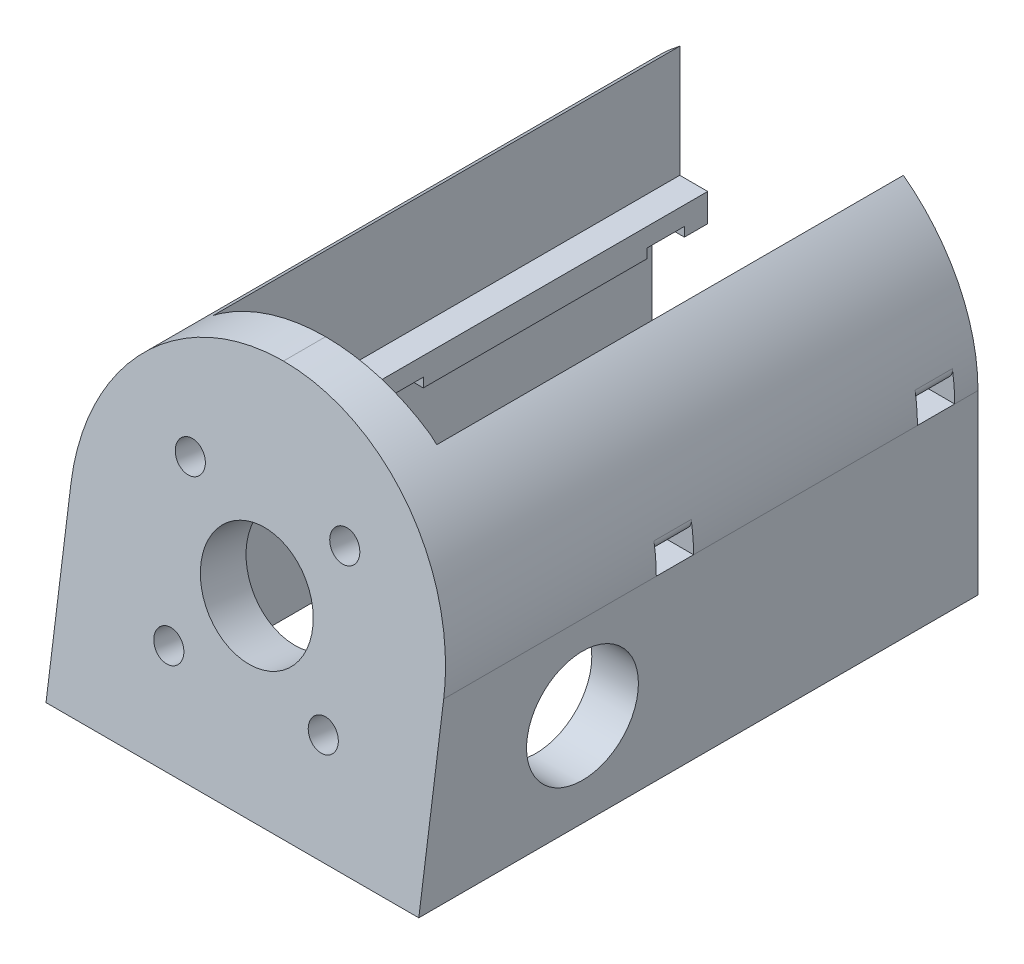
SolidWorks part; units mm, degrees
material "Shapeways \"strong flex\""
ref_plane "Front Plane" through (0, 0, 0) normal (0, 0, 1) x (1, 0, 0)
ref_plane "Top Plane" through (0, 0, 0) normal (0, 1, 0) x (1, 0, 0)
ref_plane "Right Plane" through (0, 0, 0) normal (1, 0, 0) x (0, 0, -1)
sketch "Sketch1" plane through (0, 0, 0) normal (1, 0, 0) x (0, 0, -1)
  line L0 (0, 0) -> (6.961, 49.53)
  line L1 (6.961, 49.53) -> (76.2, 49.53)
  line L2 (76.2, 0) -> (76.2, 49.53)
  line L3 (76.2, 0) -> (0, 0)
  dimension "D3" = 49.53
  dimension "D1" = 82
  dimension "D2" = 76.2
extrude "Boss-Extrude1" add sketch "Sketch1" along normal blind 25.4 and the other way blind 25.4 contours L3 L1 L0 region at (0, 24.3699, -39.8125)
sketch "Sketch3" plane through (0, 0, 0) normal (0, -1, 0) x (1, 0, 0)
  line L1 (0, -6.961) -> (0, -76.2) construction
  line L3 (-25.4, 0) -> (25.4, 0) construction
  circle A2 centre (0, -25.4) radius 8.382
  circle A4 centre (0, -63.246) radius 8.382
  dimension "D3" = 16.764
  dimension "D5" = 16.764
  dimension "D7" = 25.4
  dimension "D8" = 63.246
extrude "Cut-Extrude9" cut sketch "Sketch3" against normal through all contours A4 | A2 region at (0, 0, -63.246)
sketch "Sketch9" plane through (0, 0, -76.2) normal (0, 0, -1) x (-1, 0, 0)
  line L0 (-15.24, 49.53) -> (-15.24, 29.21)
  line L1 (-15.24, 29.21) -> (-11.43, 29.21)
  line L2 (15.24, 29.21) -> (15.24, 49.53)
  line L3 (15.24, 49.53) -> (-15.24, 49.53)
  line L5 (-11.43, 29.21) -> (-11.43, 25.4)
  line L6 (-25.4, 0) -> (-25.4, 49.53) construction
  line L7 (11.43, 25.4) -> (11.43, 29.21)
  line L8 (11.43, 29.21) -> (15.24, 29.21)
  line L9 (-11.43, 25.4) -> (-19.05, 25.4)
  line L10 (-19.05, 25.4) -> (-19.05, 0)
  line L11 (-19.05, 0) -> (19.05, 0)
  line L12 (19.05, 0) -> (19.05, 25.4)
  line L13 (19.05, 25.4) -> (11.43, 25.4)
  line L14 (25.4, 0) -> (25.4, 49.53) construction
  line L17 (25.4, 49.53) -> (-25.4, 49.53) construction
  dimension "D10" = 3.81
  dimension "D11" = 3.81
  dimension "D1" = 20.32
  dimension "D2" = 30.48
  dimension "D3" = 3.81
  dimension "D4" = 10.16
  dimension "D5" = 3.81
  dimension "D6" = 49.53
  dimension "D7" = 6.35
  dimension "D8" = 6.35
  dimension "D9" = 0
extrude "Cut-Extrude14" cut sketch "Sketch9" against normal blind 63.5 contours L3 L0 L1 L5 L9 L10 L11 L12 L13 L7 L8 L2
sketch "Sketch14" plane through (0, 0, 0) normal (0, -1, 0) x (1, 0, 0)
  line L0 (19.05, -6.35) -> (19.05, -52.972)
  line L1 (19.05, -6.35) -> (-19.05, -6.35)
  line L2 (19.05, -12.7) -> (19.05, -76.2) construction
  line L3 (-25.4, 0) -> (25.4, 0) construction
  line L4 (19.05, -52.972) -> (-19.05, -52.972)
  line L5 (-19.05, -12.7) -> (-19.05, -76.2) construction
  line L6 (-19.05, -52.972) -> (-19.05, -6.35)
  dimension "D1" = 6.35
  dimension "D2" = 46.622
  dimension "D3" = 38.1
extrude "Cut-Extrude23" cut sketch "Sketch14" against normal blind 12.7 draft 8
sketch "Sketch13" plane through (-25.4, 0, 0) normal (-1, 0, 0) x (0, 0, 1)
  line L0 (-73.025, 26.67) -> (-73.025, 24.13)
  line L1 (-73.025, 24.13) -> (-67.945, 24.13)
  line L2 (-67.945, 24.13) -> (-67.945, 26.67)
  line L3 (-67.945, 26.67) -> (-73.025, 26.67)
  line L4 (-37.441, 26.67) -> (-37.441, 24.13)
  line L5 (-37.441, 24.13) -> (-32.361, 24.13)
  line L6 (-32.361, 24.13) -> (-32.361, 26.67)
  line L7 (-32.361, 26.67) -> (-37.441, 26.67)
  line L8 (-76.2, 49.53) -> (-6.961, 49.53) construction
  line L9 (-76.2, 0) -> (-76.2, 49.53) construction
  dimension "D1" = 22.86
  dimension "D2" = 22.86
  dimension "D3" = 5.08
  dimension "D4" = 5.08
  dimension "D5" = 25.4
  dimension "D6" = 3.175
  dimension "D7" = 2.54
  dimension "D8" = 2.54
extrude "Cut-Extrude22" cut sketch "Sketch13" against normal through all contours L3 L0 L1 L2 | L7 L4 L5 L6
fillet "Fillet4" radius 25.4 2 edges at (-25.4, 49.53, -41.5805) (25.4, 49.53, -41.5805)
extrude "Cut-Extrude24" cut sketch "Sketch9<4>" against normal up to surface (65.7448 mm away) contours L3 L0 L1 L5 L9 L10 L11 L12 L13 L7 L8 L2 up to face at (0, 6.35, -7.2424)
sketch "Sketch9<4>" plane through (0, 0, -76.2) normal (0, 0, -1) x (-1, 0, 0) same geometry as "Sketch9"
sketch "Sketch17" plane through (0, 0, 0) normal (0, 0.1392, 0.9903) x (1, 0, 0)
  line L2 (-10.5249, 58.3091) -> (-10.5249, 9.9911) construction
  line L3 (-13.7462, 34.4009) -> (22.0044, 34.4009) construction
  line L4 (-11.2423, 13.3511) -> (20.3661, 13.3511) construction
  line L5 (10.5249, 1.1552) -> (10.5249, 42.8401) construction
  line L6 (-10.5249, 13.3511) -> (10.5249, 34.4009) construction
  line L7 (-25.4, 0) -> (-25.4, 24.3671) construction
  circle A0 centre (0, 23.876) radius 7.62
  circle A5 centre (-10.5249, 34.4009) radius 2.032
  circle A6 centre (10.5249, 34.4009) radius 2.032
  circle A7 centre (10.5249, 13.3511) radius 2.032
  circle A8 centre (-10.5249, 13.3511) radius 2.032
  dimension "D3" = 15.24
  dimension "D16" = 4.064
  dimension "D17" = 4.064
  dimension "D18" = 4.064
  dimension "D19" = 4.064
  dimension "D11" = 23.876
  dimension "D13" = 25.4
  dimension "D20" = 29.7688
  dimension "D21" = 29.7688
  dimension "D22" = 14.8844
  dimension "D23" = 14.8844
  dimension "D24" = 45
extrude "Cut-Extrude25" cut sketch "Sketch17" against normal through all contours A0 | A7 | A8
fillet "Fillet5" radius 1.27 4 edges at (25.2727, 26.67, -34.901) (25.2727, 26.67, -70.485) (-25.2727, 26.67, -34.901) (-25.2727, 26.67, -70.485)
extrude "Cut-Extrude26" cut sketch "Sketch17<7>" against normal blind 12.7 contours A6 | A5 region at (10.5249, 34.0661, -4.7877)
sketch "Sketch17<7>" plane through (0, 0, 0) normal (0, 0.1392, 0.9903) x (1, 0, 0) same geometry as "Sketch17"
sketch "Sketch18" plane through (25.4, 0, 0) normal (1, 0, 0) x (0, 0, -1)
  line L0 (76.2, 0) -> (0, 0) construction
  line L1 (0, 0) -> (3.3913, 24.13) construction
  circle A0 centre (22.3046, 12.7) radius 7.62
  dimension "D1" = 12.7
  dimension "D2" = 20.32
extrude "Cut-Extrude27" cut sketch "Sketch18" against normal blind 12.7
